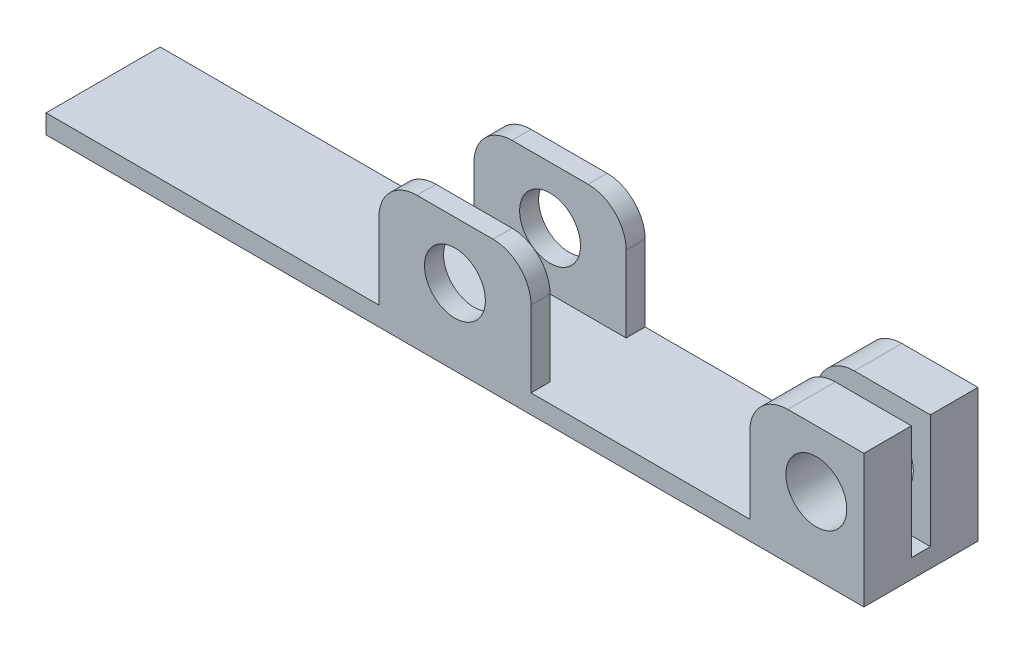
SolidWorks part; units mm, degrees
ref_plane "Front Plane" through (0, 0, 0) normal (0, 0, 1) x (1, 0, 0)
ref_plane "Top Plane" through (0, 0, 0) normal (0, 1, 0) x (1, 0, 0)
ref_plane "Right Plane" through (0, 0, 0) normal (1, 0, 0) x (0, 0, -1)
sketch "Sketch2" plane through (0, 0, 0) normal (0, 1, 0) x (1, 0, 0)
  line L1 (107.5, 15) -> (-107.5, 15)
  line L2 (107.5, 15) -> (107.5, -15)
  line L3 (107.5, -15) -> (-107.5, -15)
  line L4 (-107.5, 15) -> (-107.5, -15)
  line L5 (107.5, 15) -> (-107.5, -15) construction
  line L6 (107.5, -15) -> (-107.5, 15) construction
  point P0 (0, 0)
  dimension "D1" = 215
  dimension "D2" = 30
extrude "Boss-Extrude1" add sketch "Sketch2" along normal blind 5
sketch "HOLES TBD" plane through (0, 5, 0) normal (0, 1, 0) x (1, 0, 0)
  line L0 (100, 0) -> (-100, 0) construction
  circle A0 centre (-100, 0) radius 2.8385
  circle A1 centre (100, 0) radius 2.8385
  point P4 (0, 0)
  dimension "D2" = 5.6769
  dimension "D1" = 200
sketch "Sketch4" plane through (0, 5, 0) normal (0, 1, 0) x (1, 0, 0)
  line L0 (-107.5, -15) -> (107.5, -15) construction
  line L1 (107.5, -15) -> (77.5, -15)
  line L2 (107.5, -15) -> (107.5, -2.5)
  line L3 (107.5, -2.5) -> (77.5, -2.5)
  line L4 (77.5, -15) -> (77.5, -2.5)
  line L5 (107.5, -15) -> (77.5, -2.5) construction
  line L6 (107.5, -2.5) -> (77.5, -15) construction
  line L7 (-20, -15) -> (20, -15)
  line L8 (-20, -15) -> (-20, -10)
  line L9 (-20, -10) -> (20, -10)
  line L10 (20, -15) -> (20, -10)
  line L11 (-20, -15) -> (20, -10) construction
  line L12 (-20, -10) -> (20, -15) construction
  line L13 (0, 0) -> (0, -15) construction
  line L14 (-100, 0) -> (100, 0) construction
  line L15 (-20, 10) -> (20, 15) construction
  line L16 (-20, 15) -> (20, 10) construction
  line L17 (107.5, 2.5) -> (77.5, 15) construction
  line L18 (107.5, 15) -> (77.5, 2.5) construction
  line L19 (20, 15) -> (20, 10)
  line L20 (-20, 10) -> (20, 10)
  line L21 (-20, 15) -> (-20, 10)
  line L22 (-20, 15) -> (20, 15)
  line L23 (77.5, 15) -> (77.5, 2.5)
  line L24 (107.5, 2.5) -> (77.5, 2.5)
  line L25 (107.5, 15) -> (107.5, 2.5)
  line L26 (107.5, 15) -> (77.5, 15)
  point P4 (92.5, -8.75)
  point P10 (0, -12.5)
  point P28 (0, 12.5)
  point P29 (92.5, 8.75)
  dimension "D1" = 12.5
  dimension "D2" = 30
  dimension "D3" = 40
  dimension "D4" = 5
extrude "Boss-Extrude2" add sketch "Sketch4" along normal blind 30
sketch "Sketch5" plane through (0, 0, 15) normal (0, 0, 1) x (1, 0, 0)
  line L0 (0, 5) -> (0, 20) construction
  line L3 (0, 20) -> (95, 20) construction
  line L6 (20, 35) -> (20, 5) construction
  circle A0 centre (0, 20) radius 8
  circle A1 centre (95, 20) radius 8
  point P10 (20, 20)
  dimension "D1" = 16
  dimension "D2" = 16
  dimension "D3" = 95
extrude "Bearing holes" cut sketch "Sketch5" against normal through all
chamfer "Chamfer1" [suppressed] distance 5 angle 45
fillet "Fillet1" radius 10 6 edges at (-20, 35, 12.5) (-20, 35, -12.5) (20, 35, -12.5) (20, 35, 12.5) (77.5, 35, 8.75) (77.5, 35, -8.75)
